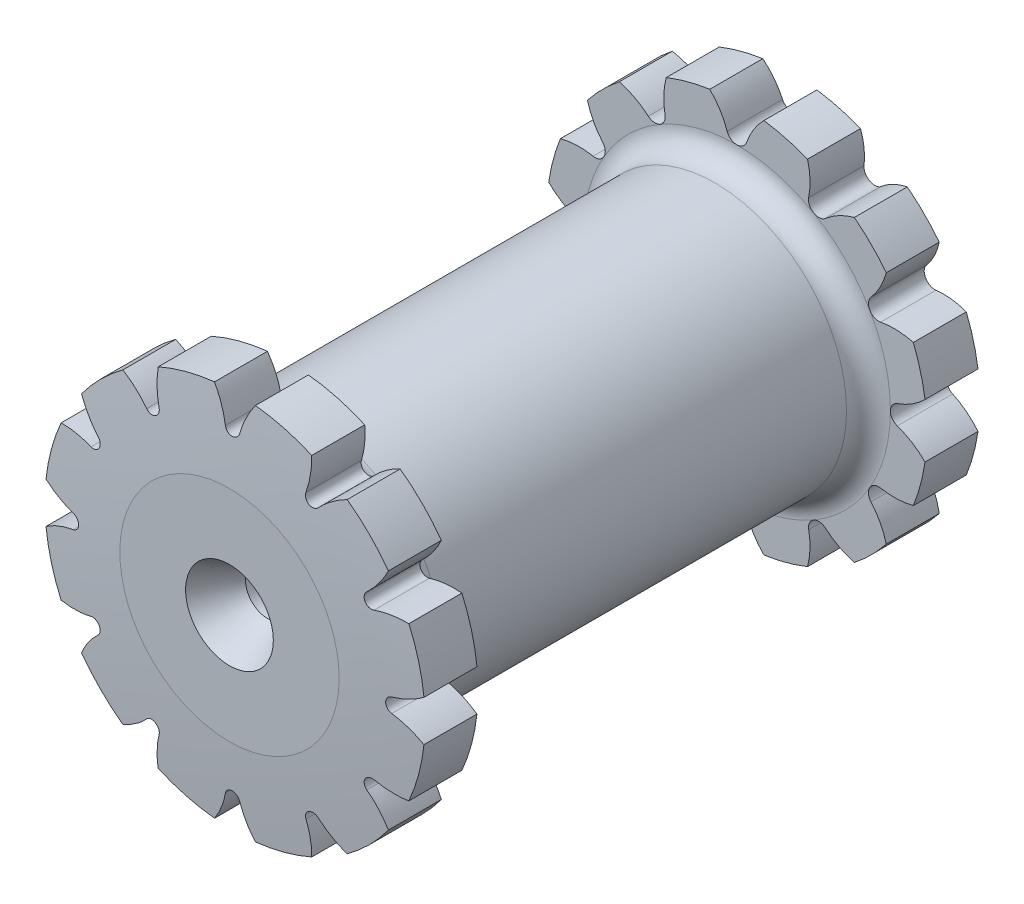
SolidWorks part; units mm, degrees
material "EN39B"
ref_plane "Front Plane" through (0, 0, 0) normal (0, 0, 1) x (1, 0, 0)
ref_plane "Top Plane" through (0, 0, 0) normal (0, 1, 0) x (1, 0, 0)
ref_plane "Right Plane" through (0, 0, 0) normal (1, 0, 0) x (0, 0, -1)
sketch "Sketch1" plane through (0, 0, 0) normal (1, 0, 0) x (0, 0, -1)
  line L0 (0, 0) -> (47.2544, 0) construction
  line L1 (0.3768, 13) -> (4, 13)
  line L2 (4, 13) -> (4, 10.5)
  line L3 (5.5, 9) -> (33.2, 9)
  line L4 (34.7, 10.5) -> (34.7, 13)
  line L5 (34.7, 13) -> (38.3232, 13)
  line L6 (38.7, 0) -> (38.7, 7.5)
  line L7 (0, 0) -> (0, 7.5)
  line L8 (0, 0) -> (38.7, 0)
  arc A0 (0, 7.5) -> (0.3768, 13) centre (149.8124, 0) cw
  arc A1 (38.7, 7.5) -> (38.3232, 13) centre (-111.1124, 0) ccw
  arc A2 (4, 10.5) -> (5.5, 9) centre (5.5, 10.5) ccw
  arc A3 (33.2, 9) -> (34.7, 10.5) centre (33.2, 10.5) ccw
  point P18 (34.7, 9)
  dimension "D7" = 150
  dimension "D8" = 15
  dimension "D10" = 150
  dimension "D12" = 1.5
  dimension "D1" = 26
  dimension "D2" = 26
  dimension "D3" = 4
  dimension "D4" = 4
  dimension "D6" = 18
  dimension "D9" = 38.7
  dimension "D11" = 15
revolve "Revolve1" add sketch "Sketch1" angle 360 about L0
sketch "Sketch2" plane through (0, 0, 0) normal (1, 0, 0) x (0, 0, -1)
  line L0 (38.7, 3) -> (36.1019, 1.5)
  line L1 (36.1019, 1.5) -> (33.6013, 1.5)
  line L2 (33.6013, 1.5) -> (32.7, 0)
  line L3 (0, 0) -> (41.5, 0) construction
  line L4 (38.7, -7.5) -> (38.7, 7.5) construction
  line L5 (38.7, 3) -> (38.7, 0)
  line L6 (32.7, 0) -> (38.7, 0)
  dimension "D1" = 3
  dimension "D2" = 30
  dimension "D3" = 59
  dimension "D4" = 6
  dimension "D5" = 6
revolve "Cut-Revolve1" cut sketch "Sketch2" angle 360 about L3
sketch "Sketch3" plane through (0, 0, 0) normal (1, 0, 0) x (0, 0, -1)
  line L0 (0, 3) -> (2.5981, 1.5)
  line L1 (2.5981, 1.5) -> (5.0987, 1.5)
  line L2 (5.0987, 1.5) -> (6, 0)
  line L3 (0, 3) -> (0, 0)
  line L4 (0, 0) -> (12.7492, 0) construction
  line L5 (6, 0) -> (0, 0)
  dimension "D1" = 6
  dimension "D2" = 30
  dimension "D3" = 59
  dimension "D4" = 3
  dimension "D5" = 6
revolve "Cut-Revolve2" cut sketch "Sketch3" angle 360 about L4
ref_plane "Plane1" through (0, 0, -40) normal (0, 0, 1) x (1, 0, 0)
sketch "Sketch4" plane through (0, 0, -40) normal (0, 0, 1) x (1, 0, 0)
  line L0 (0, 0) -> (-15.7466, 0) construction
  line L1 (0, 0) -> (0, 14.7663) construction
  arc A0 (-0.6613, 10.9706) -> (0.6613, 10.9706) centre (0, 11.2) ccw
  circle A1 centre (0, 0) radius 13 construction
  arc A2 (1.85, 12.8677) -> (-1.85, 12.8677) centre (0, 0) ccw
  arc A3 (-1.85, 12.8677) -> (-0.6613, 10.9706) centre (-5.3851, 9.3318) cw
  arc A4 (1.85, 12.8677) -> (0.6613, 10.9706) centre (5.3851, 9.3318) ccw
  dimension "D1" = 1.4
  dimension "D3" = 21
  dimension "D4" = 5
  dimension "D2" = 3.7
extrude "Cut-Extrude1" cut sketch "Sketch4" along normal up to surface (5.3 mm away) up to face at (10.5, 0, -34.7)
ref_axis "Axis1" through (0, 0, -33.2) along (0, 0, 1)
pattern_circular "CirPattern1" count 12 over 360 about axis through (0, 0, -33.2) along (0, 0, 1) of "Cut-Extrude1"
sketch "Sketch5" plane through (0, 0, 0) normal (0, 0, 1) x (1, 0, 0)
  line L0 (0, 0) -> (20.7288, 0) construction
  line L1 (0, 0) -> (0, 13.7027) construction
  circle A0 centre (0, 0) radius 13 construction
  arc A1 (1.4, 12.9244) -> (-1.4, 12.9244) centre (0, 0) ccw
  arc A2 (-0.4871, 10.8872) -> (0.4871, 10.8872) centre (0, 11) ccw
  arc A3 (1.4, 12.9244) -> (0.4871, 10.8872) centre (6.1375, 9.5783) ccw
  arc A4 (-1.4, 12.9244) -> (-0.4871, 10.8872) centre (-6.1375, 9.5783) cw
  dimension "D1" = 1
  dimension "D3" = 21
  dimension "D4" = 5.8
  dimension "D2" = 2.8
extrude "Cut-Extrude2" cut sketch "Sketch5" against normal up to surface (4 mm away) up to face at (13, 0, -4)
pattern_circular "CirPattern2" count 12 over 360 about axis through (0, 0, -33.2) along (0, 0, 1) of "Cut-Extrude2"
